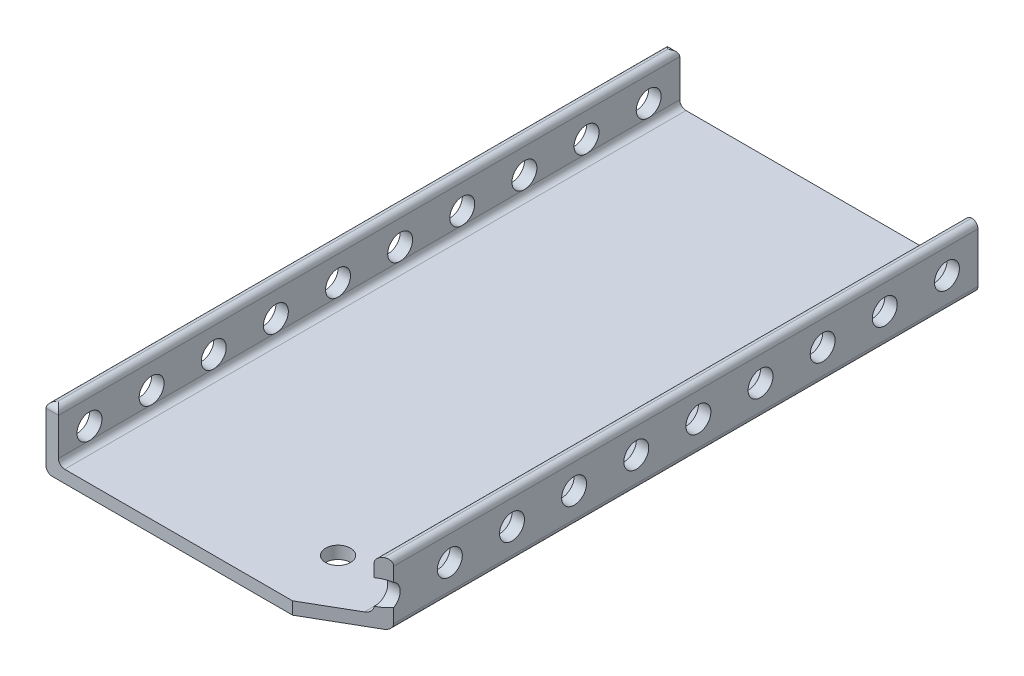
SolidWorks part; units mm, degrees
ref_plane "Front Plane" through (0, 0, 0) normal (0, 0, 1) x (1, 0, 0)
ref_plane "Top Plane" through (0, 0, 0) normal (0, 1, 0) x (1, 0, 0)
ref_plane "Right Plane" through (0, 0, 0) normal (1, 0, 0) x (0, 0, -1)
sketch "Sketch1" plane through (0, 0, 0) normal (0, 1, 0) x (1, 0, 0)
  line L1 (-25, -50) -> (25, -50)
  line L2 (-25, -50) -> (-25, 50)
  line L3 (-25, 50) -> (25, 50)
  line L4 (25, -50) -> (25, 50)
  line L5 (-25, -50) -> (25, 50) construction
  line L6 (-25, 50) -> (25, -50) construction
  point P0 (0, 0)
  dimension "D1" = 50
  dimension "D2" = 100
extrude "Boss-Extrude1" add sketch "Sketch1" along normal blind 2
sketch "Sketch2" plane through (0, 2, 0) normal (0, 1, 0) x (1, 0, 0)
  line L0 (-25, -50) -> (25, -50) construction
  line L1 (-25, 50) -> (-23, 50)
  line L2 (-25, 50) -> (-25, -50)
  line L3 (-25, -50) -> (-23, -50)
  line L4 (-23, 50) -> (-23, -50)
  line L6 (25, 50) -> (23, 50)
  line L7 (25, 50) -> (25, -50)
  line L8 (25, -50) -> (23, -50)
  line L9 (23, 50) -> (23, -50)
  dimension "D1" = 2
  dimension "D2" = 2
extrude "Boss-Extrude2" add sketch "Sketch2" along normal blind 8
fillet "Fillet1" radius 1 10 edges at (-24, 10, -50) (-23, 10, 0) (-24, 10, 50) (-25, 10, 0) (25, 0, 0) (-25, 0, 0) (25, 10, 0) (23, 10, 0) (-23, 2, 0) (23, 2, 0)
sketch "Sketch3" plane through (-25, 0, 0) normal (-1, 0, 0) x (0, 0, 1)
  line L0 (-50, 9) -> (-50, 1) construction
  line L1 (50, 9) -> (-50, 9) construction
  line L3 (50, 9) -> (50, 1) construction
  circle A0 centre (-45, 5) radius 2.005
  circle A20 centre (-35, 5) radius 2.005
  circle A21 centre (-25, 5) radius 2.005
  circle A22 centre (-15, 5) radius 2.005
  circle A23 centre (-5, 5) radius 2.005
  circle A24 centre (5, 5) radius 2.005
  circle A25 centre (15, 5) radius 2.005
  circle A26 centre (25, 5) radius 2.005
  circle A27 centre (35, 5) radius 2.005
  circle A28 centre (45, 5) radius 2.005
  dimension "D1" = 4.01
  dimension "D2" = 5
  dimension "D4" = 10
  dimension "D5" = 5
  dimension "D3" = 4
extrude "Cut-Extrude1" cut sketch "Sketch3" against normal through all
sketch "Sketch4" plane through (0, 2, 0) normal (0, 1, 0) x (1, 0, 0)
  line L0 (22, -50) -> (22, 50) construction
  line L1 (-22, -50) -> (22, -50) construction
  circle A1 centre (12, -40) radius 2.005
  dimension "D1" = 4.01
  dimension "D2" = 10
  dimension "D3" = 10
extrude "Cut-Extrude2" cut sketch "Sketch4" against normal blind 10 contours A1
sketch "Sketch5" plane through (0, 0, 0) normal (0, -1, 0) x (1, 0, 0)
  line L0 (25, 50) -> (14.68, 50)
  line L1 (-24, 50) -> (24, 50) construction
  line L2 (14.68, 50) -> (25, 44.04)
  line L3 (25, 50) -> (25, -50) construction
  line L4 (25, 44.04) -> (25, 50)
  dimension "D1" = 10.32
  dimension "D2" = 5.96
extrude "Cut-Extrude3" cut sketch "Sketch5" against normal through all
